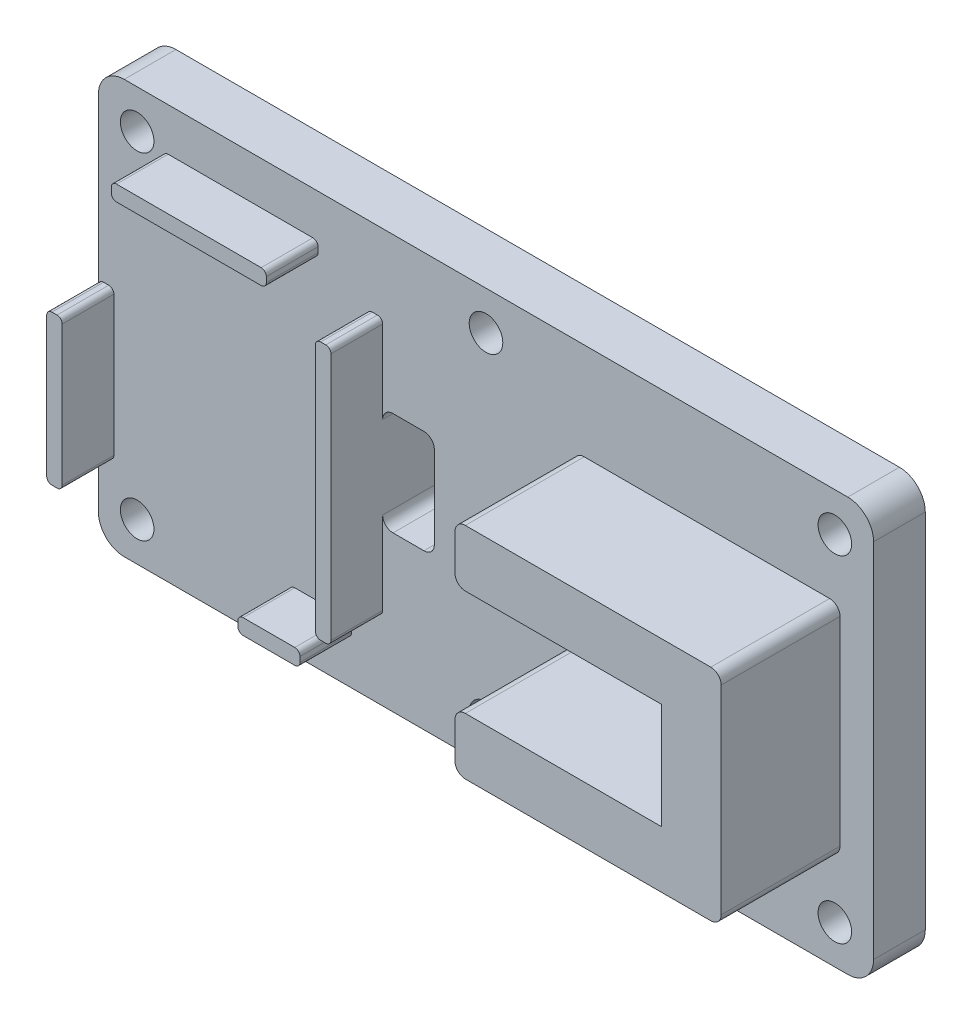
SolidWorks part; units mm, degrees
ref_plane "Front Plane" through (0, 0, 0) normal (0, 0, 1) x (1, 0, 0)
ref_plane "Top Plane" through (0, 0, 0) normal (0, 1, 0) x (1, 0, 0)
ref_plane "Right Plane" through (0, 0, 0) normal (1, 0, 0) x (0, 0, -1)
sketch "Sketch1" plane through (0, 0, 0) normal (0, 0, 1) x (1, 0, 0)
  line L1 (-75, 40) -> (75, 40)
  line L2 (-75, 40) -> (-75, -40)
  line L3 (-75, -40) -> (75, -40)
  line L4 (75, 40) -> (75, -40)
  line L5 (-75, 40) -> (75, -40) construction
  line L6 (-75, -40) -> (75, 40) construction
  line L7 (-20, 10) -> (-10, 10)
  line L8 (-20, 10) -> (-20, -10)
  line L9 (-20, -10) -> (-10, -10)
  line L10 (-10, 10) -> (-10, -10)
  line L11 (-20, 10) -> (-10, -10) construction
  line L12 (-20, -10) -> (-10, 10) construction
  point P0 (0, 0)
  point P6 (-15, 0)
  dimension "D1" = 80
  dimension "D2" = 150
  dimension "D3" = 20
  dimension "D4" = 10
  dimension "D5" = 90
extrude "Boss-Extrude1" add sketch "Sketch1" along normal blind 10
fillet "Fillet1" radius 2 4 edges at (-20, -10, 5) (-10, -10, 5) (-10, 10, 5) (-20, 10, 5)
fillet "Fillet2" radius 5 4 edges at (-75, 40, 5) (-75, -40, 5) (75, -40, 5) (75, 40, 5)
sketch "Sketch2" plane through (0, 0, 10) normal (0, 0, 1) x (1, 0, 0)
  line L1 (57, -10.25) -> (22.5, -10.25)
  line L2 (57, -10.25) -> (57, 10.25)
  line L3 (57, 10.25) -> (22.5, 10.25)
  line L5 (57, -10.25) -> (22.5, 10.25) construction
  line L6 (57, 10.25) -> (22.5, -10.25) construction
  line L10 (22.5, 10.25) -> (11, 10.25)
  line L14 (68.5, -21.25) -> (11, -21.25)
  line L15 (68.5, -21.25) -> (68.5, 21.25)
  line L16 (22.5, 10.25) -> (22.5, -10.25)
  line L17 (75, -35) -> (75, 35) construction
  line L18 (68.5, 21.25) -> (11, 21.25)
  line L19 (11, -21.25) -> (11, -10.25)
  line L20 (68.5, -21.25) -> (11, 21.25) construction
  line L21 (68.5, 21.25) -> (11, -21.25) construction
  line L22 (22.5, -10.25) -> (11, -10.25)
  line L23 (11, 10.25) -> (11, 21.25)
  point P0 (39.75, 0)
  point P6 (39.75, 0)
  dimension "D2" = 34.5
  dimension "D3" = 20.5
  dimension "D4" = 18
  dimension "D1" = 11
  dimension "D5" = 11.5
extrude "Boss-Extrude2" add sketch "Sketch2" along normal blind 23 contours L3 L2 L1 L15 region at (57.715, 0, 10)
extrude "Cut-Extrude1" cut sketch "Sketch2<3>" against normal up to surface (10 mm away) contours L3 L16 L1 L2 region at (39.75, 0, 10) up to face at (0, 0, 0)
sketch "Sketch2<3>" plane through (0, 0, 10) normal (0, 0, 1) x (1, 0, 0) same geometry as "Sketch2"
sketch "Sketch3" plane through (0, 0, 10) normal (0, 0, 1) x (1, 0, 0)
  line L1 (22.5, 10.25) -> (27.5, 10.25)
  line L2 (22.5, 10.25) -> (22.5, -10.25)
  line L3 (22.5, -10.25) -> (27.5, -10.25)
  line L4 (27.5, 10.25) -> (27.5, -10.25)
  line L5 (27.5, 10.25) -> (52, 10.25) construction
  line L6 (57, 10.25) -> (52, 10.25)
  line L7 (57, 10.25) -> (57, -10.25)
  line L8 (57, -10.25) -> (52, -10.25)
  line L9 (52, 10.25) -> (52, -10.25)
  line L10 (54.75, -8) -> (24.75, -8) construction
  line L11 (54.75, -8) -> (54.75, 8) construction
  line L12 (54.75, 8) -> (24.75, 8) construction
  line L13 (24.75, -8) -> (24.75, 8) construction
  line L14 (54.75, -8) -> (24.75, 8) construction
  line L15 (54.75, 8) -> (24.75, -8) construction
  circle A0 centre (24.75, 8) radius 1.1
  circle A1 centre (24.75, -8) radius 1.1
  circle A2 centre (54.75, 8) radius 1.1
  circle A3 centre (54.75, -8) radius 1.1
  point P12 (39.75, 10.25)
  point P21 (39.75, 0)
  dimension "D2" = 2.2
  dimension "D1" = 5
  dimension "D3" = 30
  dimension "D4" = 16
extrude "Boss-Extrude3" add sketch "Sketch3" against normal blind 3
sketch "Sketch4" plane through (0, 0, 7) normal (0, 0, -1) x (-1, 0, 0)
  line L1 (-22.5, 10.25) -> (-57, 10.25)
  line L2 (-22.5, 10.25) -> (-22.5, -10.25)
  line L3 (-22.5, -10.25) -> (-57, -10.25)
  line L4 (-57, 10.25) -> (-57, -10.25)
sketch "Sketch5" plane through (0, 0, 0) normal (0, 0, -1) x (-1, 0, 0)
  line L1 (-67, -18.25) -> (-12.5, -18.25)
  line L2 (-67, -18.25) -> (-67, 18.25)
  line L3 (-67, 18.25) -> (-12.5, 18.25)
  line L4 (-22.5, 10.25) -> (-57, 10.25)
  line L5 (-57, 10.25) -> (-57, -10.25)
  line L6 (-57, -10.25) -> (-22.5, -10.25)
  line L7 (-22.5, -10.25) -> (-22.5, 10.25)
  line L8 (-22.5, 10.25) -> (-57, 10.25) construction
  line L9 (-57, 10.25) -> (-57, -10.25) construction
  line L10 (-57, -10.25) -> (-22.5, -10.25) construction
  line L11 (-22.5, -10.25) -> (-22.5, 10.25) construction
  line L12 (-12.5, -18.25) -> (-12.5, 18.25)
  line L13 (-67, -18.25) -> (-12.5, 18.25) construction
  line L14 (-67, 18.25) -> (-12.5, -18.25) construction
  point P2 (-39.75, 0)
  point P12 (-39.75, 10.25)
  dimension "D2" = 10
  dimension "D3" = 8
  dimension "D1" = 0
loft "Cut-Loft2" cut profiles "Sketch4", "Sketch5" connector at (22.5, 10.25, 7) connector at (12.5, 18.25, 0)
sketch "Sketch6" plane through (-10, 0, 0) normal (-1, 0, 0) x (0, 0, 1)
  line L0 (0, 6) -> (0, -6)
  arc A0 (0, -6) -> (0, 6) centre (0, 0) ccw
  dimension "D1" = 6
extrude "Cut-Extrude2" cut sketch "Sketch6" against normal up to surface (22.5 mm away) up to face at (20, -4.5625, 5.25)
sketch "Sketch7" plane through (0, 0, 7) normal (0, 0, -1) x (-1, 0, 0)
  line L0 (-57, 10.25) -> (-57, -10.25) construction
  line L1 (-57, -10.25) -> (-52, -10.25) construction
  line L2 (-52, -10.25) -> (-52, 10.25) construction
  line L3 (-52, 10.25) -> (-57, 10.25) construction
  line L4 (-22.5, -10.25) -> (-22.5, 10.25) construction
  line L5 (-22.5, 10.25) -> (-27.5, 10.25) construction
  line L6 (-27.5, 10.25) -> (-27.5, -10.25) construction
  line L7 (-27.5, -10.25) -> (-22.5, -10.25) construction
  line L8 (-57, 10.25) -> (-57, -10.25)
  line L9 (-57, -10.25) -> (-52, -10.25)
  line L10 (-52, -10.25) -> (-52, 10.25)
  line L11 (-52, 10.25) -> (-57, 10.25)
  line L12 (-22.5, -10.25) -> (-22.5, 10.25)
  line L13 (-22.5, 10.25) -> (-27.5, 10.25)
  line L14 (-27.5, 10.25) -> (-27.5, -10.25)
  line L15 (-27.5, -10.25) -> (-22.5, -10.25)
extrude "Cut-Extrude3" cut sketch "Sketch7" against normal offset from surface (1 mm away) 2 up to face at (29.5, 0, 10)
sketch "Sketch14" plane through (11, 0, 0) normal (-1, 0, 0) x (0, 0, 1)
  line L0 (10, -10.25) -> (10, -21.25) construction
  line L1 (10, -21.25) -> (33, -21.25) construction
  line L2 (33, -21.25) -> (33, -10.25) construction
  line L3 (33, -10.25) -> (10, -10.25) construction
  line L4 (10, 21.25) -> (10, 10.25) construction
  line L5 (10, 10.25) -> (33, 10.25) construction
  line L6 (33, 10.25) -> (33, 21.25) construction
  line L7 (33, 21.25) -> (10, 21.25) construction
  line L8 (10, -10.25) -> (10, -21.25)
  line L9 (10, -21.25) -> (33, -21.25)
  line L10 (33, -21.25) -> (33, -10.25)
  line L11 (33, -10.25) -> (10, -10.25)
  line L12 (10, 21.25) -> (10, 10.25)
  line L13 (10, 10.25) -> (33, 10.25)
  line L14 (33, 10.25) -> (33, 21.25)
  line L15 (33, 21.25) -> (10, 21.25)
extrude "Cut-Extrude4" cut sketch "Sketch14" against normal blind 6
fillet "Fillet4" radius 1 4 edges
sketch "Sketch15" plane through (0, 0, 10) normal (0, 0, 1) x (1, 0, 0)
  line L0 (-75, 35) -> (-75, -35) construction
  line L1 (67.5, -32.5) -> (-67.5, -32.5) construction
  line L2 (67.5, -32.5) -> (67.5, 32.5) construction
  line L3 (67.5, 32.5) -> (-67.5, 32.5) construction
  line L4 (-67.5, -32.5) -> (-67.5, 32.5) construction
  line L5 (67.5, -32.5) -> (-67.5, 32.5) construction
  line L6 (67.5, 32.5) -> (-67.5, -32.5) construction
  line L7 (70, 40) -> (-70, 40) construction
  circle A0 centre (-67.5, 32.5) radius 3.25
  circle A1 centre (0, 32.5) radius 3.25
  circle A2 centre (67.5, 32.5) radius 3.25
  circle A3 centre (67.5, -32.5) radius 3.25
  circle A4 centre (0, -32.5) radius 3.25
  circle A5 centre (-67.5, -32.5) radius 3.25
  point P13 (0, 0)
  point P26 (0, 32.5)
  point P27 (0, -32.5)
  dimension "D3" = 6.5
  dimension "D1" = 7.5
  dimension "D2" = 7.5
extrude "Cut-Extrude5" cut sketch "Sketch15" against normal up to surface (10 mm away) up to face at (4.1563, 0.375, 0)
sketch "Sketch16" plane through (0, 0, 10) normal (0, 0, 1) x (1, 0, 0)
  line L0 (-75, 35) -> (-75, -35) construction
  line L1 (-49, 24.05) -> (-30, 24.05)
  line L2 (-49, 24.05) -> (-49, -24.05)
  line L3 (-49, -24.05) -> (-30, -24.05)
  line L4 (-30, 24.05) -> (-30, -24.05)
  line L5 (-54, 29.05) -> (-54, -29.05)
  line L6 (-54, -29.05) -> (-25, -29.05)
  line L7 (-25, 29.05) -> (-25, -29.05)
  line L8 (-54, 29.05) -> (-25, 29.05)
  line L9 (-20, 8) -> (-20, -8) construction
  line L10 (-49, -24.05) -> (-49, -29.05)
  line L11 (-30, -24.05) -> (-30, -29.05)
  point P6 (-75, 0)
  point P7 (-49, 0)
  dimension "D1" = 19
  dimension "D2" = 48.1
  dimension "D4" = 5
  dimension "D3" = 5
extrude "Boss-Extrude8" add sketch "Sketch16" along normal blind 15 contours L4 L11 L6 L7 L8 L5 L10 L2 L1 region at (-49.6494, 0, 10)
extrude "Boss-Extrude9" add sketch "Sketch16<3>" along normal blind 5 contours L11 L3 L10 L6 region at (-39.5, -26.55, 10)
sketch "Sketch16<3>" plane through (0, 0, 10) normal (0, 0, 1) x (1, 0, 0) same geometry as "Sketch16"
sketch "Sketch17" plane through (0, 0, 25) normal (0, 0, 1) x (1, 0, 0)
  line L3 (-30, -29.05) -> (-25, -29.05) construction
  line L4 (-49, 24.05) -> (-30, 24.05) construction
  line L5 (-54, -29.05) -> (-49, -29.05) construction
  circle A0 centre (-27.5, 3.05) radius 1.7
  circle A1 centre (-51.5, -6.95) radius 1.7
  point P8 (-51.5, -29.05)
  point P12 (-27.5, -29.05)
  dimension "D1" = 3.4
  dimension "D2" = 21
  dimension "D3" = 31
extrude "Cut-Extrude6" cut sketch "Sketch17" against normal blind 4
fillet "Fillet10" radius 2 2 edges at (-49, -26.55, 15) (-30, -26.55, 15)
fillet "Fillet11" radius 2 8 edges at (-54, -29.05, 17.5) (-25, -29.05, 17.5) (-39.5, -29.05, 10) (-54, 29.05, 17.5) (-25, 29.05, 17.5) (-25, 0, 10) (-39.5, 29.05, 10) (-54, 0, 10)
sketch "Sketch18" plane through (0, 0, 10) normal (0, 0, 1) x (1, 0, 0)
  line L1 (-67.5, 32.5) -> (0, 32.5)
  line L2 (-67.5, 32.5) -> (-67.5, -32.5)
  line L3 (-67.5, -32.5) -> (0, -32.5)
  line L4 (0, 32.5) -> (0, -32.5)
extrude "Cut-Extrude7" cut sketch "Sketch18" along normal through all
sketch "Sketch20" plane through (0, 0, 10) normal (0, 0, 1) x (1, 0, 0)
  line L0 (-75, 35) -> (-75, -35) construction
  line L1 (-75, 25) -> (-72, 25)
  line L2 (-75, 25) -> (-75, -25)
  line L3 (-75, -25) -> (-72, -25)
  line L4 (-72, 25) -> (-72, -25)
  line L5 (-20, 8) -> (-20, -8) construction
  line L6 (-23, 25) -> (-20, 25)
  line L7 (-23, 25) -> (-23, -25)
  line L8 (-23, -25) -> (-20, -25)
  line L9 (-20, 25) -> (-20, -25)
  point P6 (-75, 0)
  point P13 (-23, 0)
  dimension "D1" = 50
  dimension "D2" = 3
  dimension "D3" = 50
  dimension "D4" = 3
extrude "Boss-Extrude11" add sketch "Sketch20" along normal blind 10
fillet "Fillet13" radius 1 4 edges at (-75, 25, 15) (-72, 25, 15) (-72, -25, 15) (-75, -25, 15)
fillet "Fillet14" radius 1 4 edges at (-20, 25, 15) (-23, 25, 15) (-23, -25, 15) (-20, -25, 15)
sketch "Sketch21" plane through (-75, 0, 0) normal (-1, 0, 0) x (0, 0, 1)
  line L0 (20, 24) -> (20, -24) construction
  line L1 (20, 4) -> (10, 4)
  line L2 (20, 4) -> (20, 34)
  line L3 (20, 34) -> (10, 34)
  line L4 (10, 4) -> (10, 34)
  line L5 (10, 35) -> (10, 24) construction
  line L6 (20, 24) -> (10, 24) construction
  dimension "D1" = 20
  dimension "D2" = 30
extrude "Cut-Extrude8" cut sketch "Sketch21" against normal up to next
fillet "Fillet15" radius 1 2 edges at (-72, 4, 15) (-75, 4, 15)
sketch "Sketch22" plane through (0, 0, 10) normal (0, 0, 1) x (1, 0, 0)
  line L0 (-20, 0) -> (-75, 0) construction
  line L1 (-62.5, 31.7) -> (-32.5, 31.7)
  line L2 (-62.5, 31.7) -> (-62.5, 28.7)
  line L3 (-62.5, 28.7) -> (-32.5, 28.7)
  line L4 (-32.5, 31.7) -> (-32.5, 28.7)
  line L6 (-75, 35) -> (-75, 3) construction
  line L7 (-20, -24) -> (-20, 24) construction
  line L8 (-23, 24) -> (-23, -24) construction
  line L9 (-38, -28.7) -> (-26, -28.7)
  line L10 (-38, -28.7) -> (-38, -31.7)
  line L11 (-38, -31.7) -> (-26, -31.7)
  line L12 (-26, -28.7) -> (-26, -31.7)
  point P11 (-47.5, 28.7)
  point P12 (-47.5, 0)
  dimension "D2" = 3
  dimension "D4" = 3
  dimension "D1" = 28.7
  dimension "D3" = 30
  dimension "D5" = 28.7
  dimension "D6" = 3
  dimension "D7" = 12
extrude "Boss-Extrude12" add sketch "Sketch22" along normal blind 10
fillet "Fillet16" radius 1 4 edges at (-32.5, 28.7, 15) (-32.5, 31.7, 15) (-62.5, 31.7, 15) (-62.5, 28.7, 15)
fillet "Fillet17" radius 1 4 edges at (-26, -28.7, 15) (-38, -28.7, 15) (-26, -31.7, 15) (-38, -31.7, 15)
fillet "Fillet18" radius 2 6 edges at (68.5, 21.25, 21.5) (68.5, -21.25, 21.5) (17, -21.25, 21.5) (17, -10.25, 21.5) (17, 10.25, 21.5) (17, 21.25, 21.5)
equation "\"D3@Sketch20\"=\"D1@Sketch20\""
equation "\"D5@Sketch22\"=\"D1@Sketch22\""
